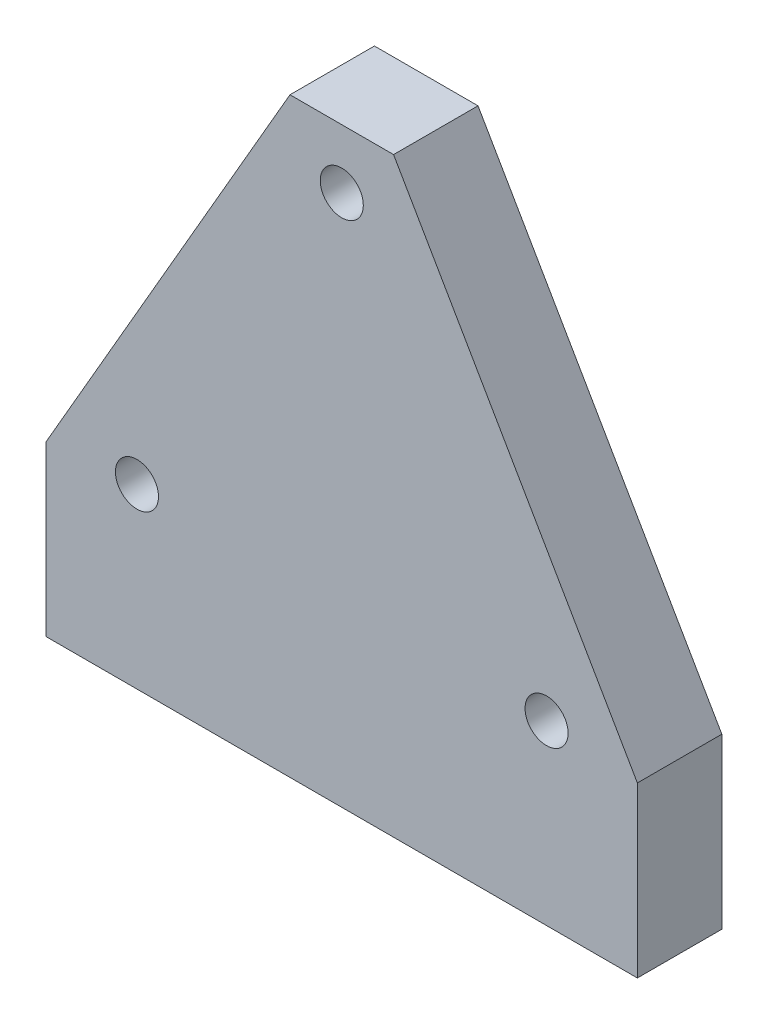
SolidWorks part; units mm, degrees
ref_plane "Ebene vorne" through (0, 0, 0) normal (0, 0, 1) x (1, 0, 0)
ref_plane "Ebene oben" through (0, 0, 0) normal (0, 1, 0) x (1, 0, 0)
ref_plane "Ebene rechts" through (0, 0, 0) normal (1, 0, 0) x (0, 0, -1)
sketch "Skizze2" plane through (0, 0, 0) normal (0, 0, 1) x (1, 0, 0)
  line L1 (0, 0) -> (70, 0)
  line L2 (0, 0) -> (0, 70)
  line L3 (0, 70) -> (70, 70)
  line L4 (70, 0) -> (70, 70)
  dimension "D1" = 70
  dimension "D2" = 70
extrude "Aufsatz-Linear austragen2" add sketch "Skizze2" along normal blind 10
sketch "Skizze4" plane through (0, 0, 10) normal (0, 0, 1) x (1, 0, 0)
  line L0 (0, 70) -> (0, 0) construction
  line L1 (0, 0) -> (70, 0) construction
  point P0 (35, 35)
  dimension "D1" = 35
  dimension "D2" = 35
ref_axis "Achse1" through (35, 35, -3.1079) along (0, 0, 1)
sketch "Skizze5" plane through (0, 0, 10) normal (0, 0, 1) x (1, 0, 0)
  line L0 (70, 0) -> (70, 70) construction
  circle A2 centre (35, 63) radius 2.55
  circle A3 centre (59.2487, 21) radius 2.55
  circle A4 centre (10.7513, 21) radius 2.55
  point P12 (35, 35)
  dimension "D1" = 3
  dimension "D3" = 5.1
  dimension "D4" = 28
  dimension "D5" = 35
extrude "Schnitt-Linear austragen1" cut sketch "Skizze5" against normal blind 10
chamfer "Fase2" distance 50 angle 30 1 edges at (70, 70, 5) first distance on face at (70, 35, 5)
chamfer "Fase3" distance 50 angle 30 1 edges at (0, 70, 5) first distance on face at (0, 35, 5)
